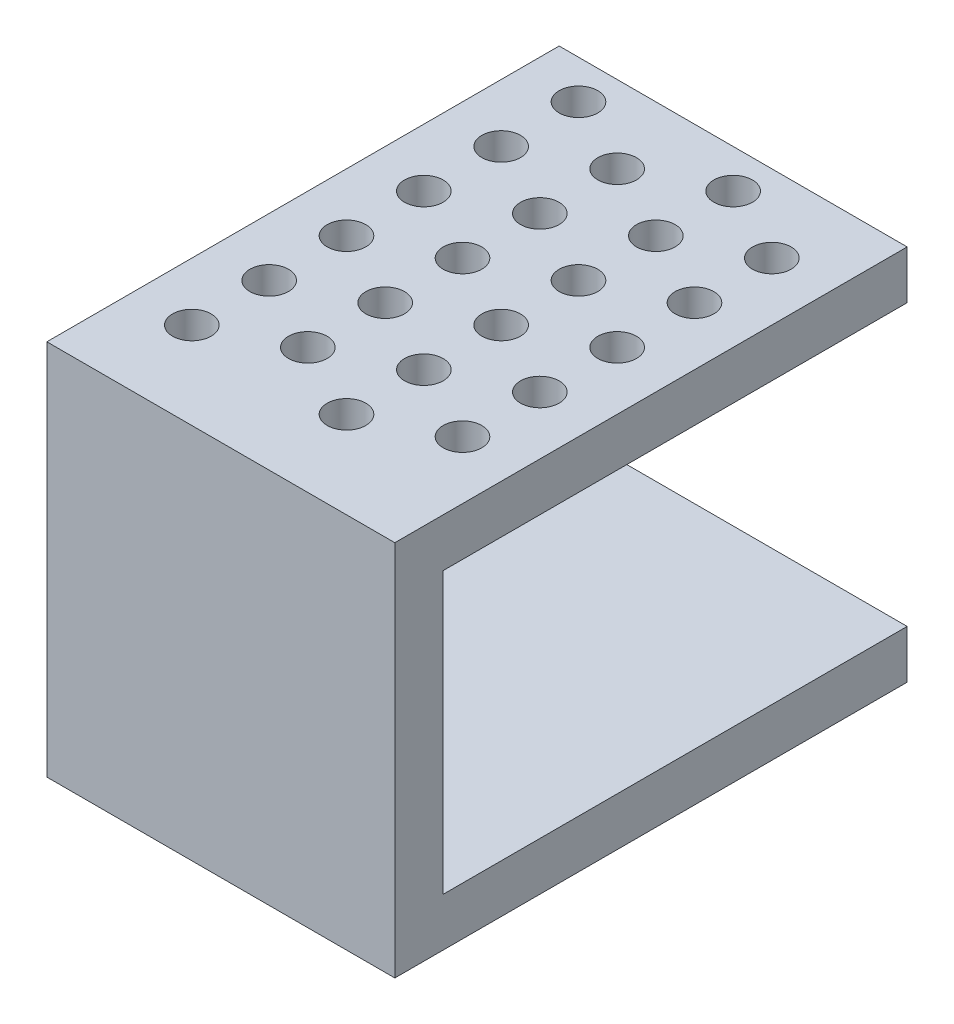
SolidWorks part; units mm, degrees
ref_plane "Front Plane" through (0, 0, 0) normal (0, 0, 1) x (1, 0, 0)
ref_plane "Top Plane" through (0, 0, 0) normal (0, 1, 0) x (1, 0, 0)
ref_plane "Right Plane" through (0, 0, 0) normal (1, 0, 0) x (0, 0, -1)
sketch "Sketch2" plane through (0, 0, 0) normal (0, 1, 0) x (1, 0, 0)
  line L1 (-20, 16) -> (-2, 16)
  line L2 (-20, 16) -> (-20, -8)
  line L3 (-20, -8) -> (-2, -8)
  line L4 (-2, 16) -> (-2, -8)
  circle A0 centre (-17, -6) radius 1
  circle A1 centre (-17, -2) radius 1
  circle A2 centre (-17, 2) radius 1
  circle A3 centre (-17, 6) radius 1
  circle A4 centre (-17, 10) radius 1
  circle A5 centre (-17, 14) radius 1
  circle A6 centre (-13, -4) radius 1
  circle A7 centre (-13, 0) radius 1
  circle A8 centre (-13, 4) radius 1
  circle A9 centre (-13, 8) radius 1
  circle A10 centre (-13, 12) radius 1
  circle A11 centre (-9, -6) radius 1
  circle A12 centre (-9, -2) radius 1
  circle A13 centre (-9, 2) radius 1
  circle A14 centre (-9, 6) radius 1
  circle A15 centre (-9, 10) radius 1
  circle A16 centre (-9, 14) radius 1
  circle A17 centre (-5, -4) radius 1
  circle A18 centre (-5, 0) radius 1
  circle A19 centre (-5, 4) radius 1
  circle A20 centre (-5, 8) radius 1
  circle A21 centre (-5, 12) radius 1
  dimension "D1" = 24
  dimension "D2" = 18
extrude "Boss-Extrude2" add sketch "Sketch2" along normal blind 2.5
sketch "Sketch3" plane through (0, 0, 8) normal (0, 0, 1) x (1, 0, 0)
  line L1 (-20, 2.5) -> (-2, 2.5)
  line L2 (-20, 2.5) -> (-20, 0)
  line L3 (-20, 0) -> (-2, 0)
  line L4 (-2, 2.5) -> (-2, 0)
extrude "Boss-Extrude3" add sketch "Sketch3" along normal blind 2.5
sketch "Sketch4" plane through (0, 0, 0) normal (0, -1, 0) x (-1, 0, 0)
  line L0 (20, 16) -> (20, -10.5) construction
  line L1 (2, -10.5) -> (20, -10.5)
  line L2 (2, -10.5) -> (2, -8)
  line L3 (2, -8) -> (20, -8)
  line L4 (20, -10.5) -> (20, -8)
  dimension "D1" = 2.5
extrude "Boss-Extrude4" add sketch "Sketch4" along normal blind 17
sketch "Sketch5" plane through (0, 0, 8) normal (0, 0, -1) x (-1, 0, 0)
  line L0 (20, -17) -> (20, 0) construction
  line L1 (2, -17) -> (20, -17)
  line L2 (2, -17) -> (2, -14.5)
  line L3 (2, -14.5) -> (20, -14.5)
  line L4 (20, -17) -> (20, -14.5)
  dimension "D1" = 2.5
extrude "Boss-Extrude5" add sketch "Sketch5" along normal blind 24
